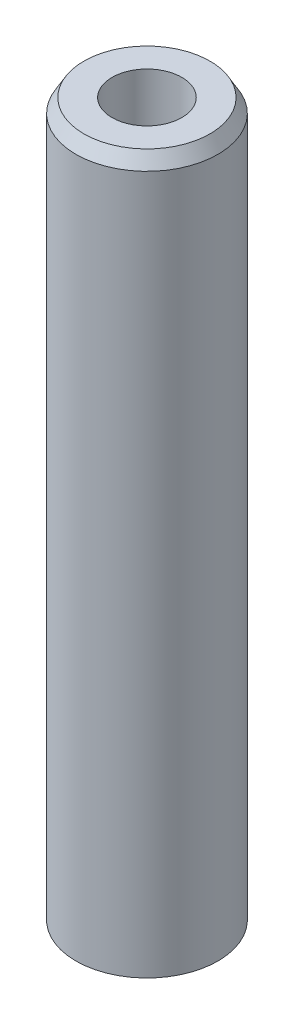
SolidWorks part; units mm, degrees
ref_plane "Front Plane" through (0, 0, 0) normal (0, 0, 1) x (1, 0, 0)
ref_plane "Top Plane" through (0, 0, 0) normal (0, 1, 0) x (1, 0, 0)
ref_plane "Right Plane" through (0, 0, 0) normal (1, 0, 0) x (0, 0, -1)
sketch "Sketch1" plane through (0, 0, 0) normal (0, 1, 0) x (1, 0, 0)
  circle A0 centre (0, 0) radius 10
  dimension "SHAFT_OD" = 20
extrude "Boss-Extrude1" add sketch "Sketch1" along normal blind 101.454
sketch "Sketch2" plane through (0, 0, 0) normal (0, 1, 0) x (1, 0, 0)
  circle A0 centre (0, 0) radius 4.9143
  dimension "BORE_D" = 9.8286
extrude "Cut-Extrude1" cut sketch "Sketch2" along normal through all
chamfer "Chamfer1" distance 1.9403 angle 30 2 edges at (0, 101.454, 10) (0, 0, 10) first distance on face at (0, 101.454, 10) first distance on face at (0, 0, 4.9143)
